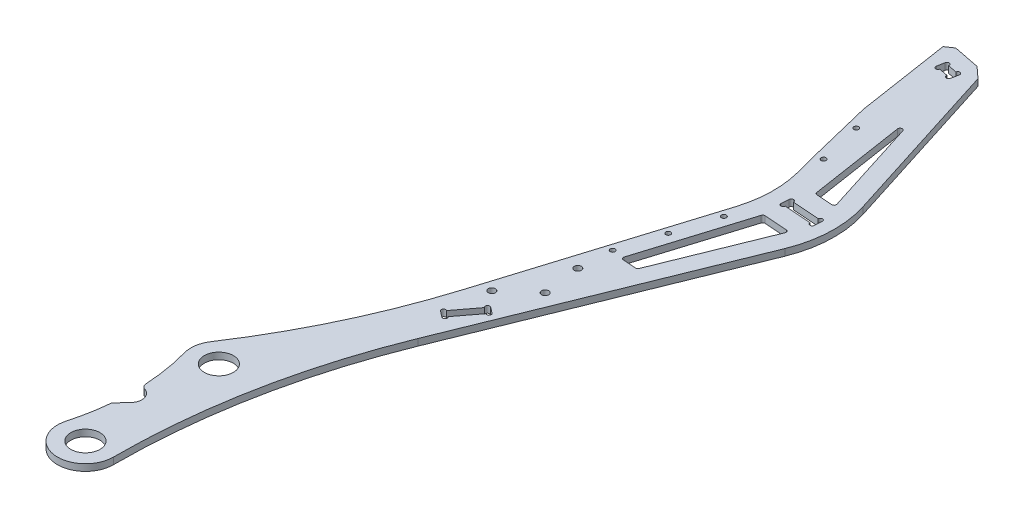
SolidWorks part; units mm, degrees
note: The reader was unsure of these and kept them because the rebuilt part matched: shared geometry of "草图7<3>".
material "碳板"
ref_plane "前视基准面" through (0, 0, 0) normal (0, 0, 1) x (1, 0, 0)
ref_plane "上视基准面" through (0, 0, 0) normal (0, 1, 0) x (1, 0, 0)
ref_plane "右视基准面" through (0, 0, 0) normal (1, 0, 0) x (0, 0, -1)
sketch "草图1" plane through (0, 0, 0) normal (0, 1, 0) x (1, 0, 0)
  line L0 (98.8372, 468.2646) -> (138.372, 211.288) construction
  line L1 (-58.327, 371.8311) -> (-50.4447, 320.5961) construction
  line L3 (-369.7364, 0) -> (416.5856, 0) construction
  line L4 (82.5, 489.7909) -> (82.5, -147.2883) construction
  line L5 (82.5, 0) -> (82.5, -60)
  line L6 (82.5, 0) -> (141.6477, 191.0538)
  line L7 (141.6477, 191.0538) -> (127.4573, 249.3516)
  line L8 (-53.7093, 374.6988) -> (-44.882, 317.3209)
  line L9 (93.8953, 467.5044) -> (133.4302, 210.5277)
  line L10 (0, 453.0589) -> (0, 190) construction
  line L11 (0, 190) -> (0, 570.1788) construction
  arc A0 (98.8372, 468.2646) -> (-58.327, 371.8311) centre (0, 453.0589) ccw construction
  arc A1 (-50.4447, 320.5961) -> (138.372, 211.288) centre (0, 190) ccw construction
  arc A2 (93.8953, 467.5044) -> (-53.7093, 374.6988) centre (0, 453.0589) ccw
  arc A3 (-44.882, 317.3209) -> (133.4302, 210.5277) centre (0, 190) ccw
  point P6 (0, 50)
  dimension "D1" = 100
  dimension "D2" = 140
  dimension "D3" = 260
  dimension "D4" = 170
  dimension "D5" = 82.5
  dimension "D6" = 190
  dimension "D7" = 60
  dimension "D8" = 200
  dimension "D9" = 60
  dimension "D10" = 5
sketch "草图3" plane through (0, 0, 0) normal (0, 1, 0) x (1, 0, 0)
  line L1 (128.8685, 240.1789) -> (141.6477, 191.0538)
  line L3 (82.5, 0) -> (82.6627, 0.5254)
  line L4 (82.5, 0) -> (82.5, -60) construction
  line L5 (82.5, 0) -> (82.5, -60) construction
  line L6 (93.8953, 467.5044) -> (133.4302, 210.5277) construction
  line L7 (82.5, 200489.7909) -> (82.5, -200147.2883) construction
  line L8 (98.2597, 7.4607) -> (171.5712, 188.9129)
  line L9 (-200369.7364, 0) -> (200416.5856, 0) construction
  line L10 (93.8953, 467.5044) -> (133.4302, 210.5277) construction
  line L11 (140.881, 285.6943) -> (171.5712, 188.9129)
  line L12 (141.6477, 191.0538) -> (171.5712, 188.9129) construction
  line L13 (108.4299, 83.7565) -> (141.6477, 191.0538)
  line L15 (128.8685, 240.1789) -> (121.2656, 289.5975)
  line L16 (121.2656, 289.5975) -> (140.881, 285.6943)
  circle A0 centre (82.5, 0) radius 6.55
  circle A1 centre (82.5, -60) radius 6.55
  circle A2 centre (82.5, 0) radius 12.55
  circle A3 centre (82.5, -60) radius 12.55
  circle A4 centre (82.5, 0) radius 0.55
  circle A5 centre (82.5, -60) radius 0.55
  arc A6 (70.404, -3.3452) -> (70.404, -56.6548) centre (-25.9781, -30) cw
  arc A7 (94.596, -3.3452) -> (94.596, -56.6548) centre (190.9781, -30) ccw
  circle A8 centre (190.9781, -30) radius 100 construction
  arc A9 (72.0339, 6.9256) -> (108.4299, 83.7565) centre (-178.1508, 172.478) ccw
  arc A11 (98.2597, 7.4607) -> (94.596, -3.3452) centre (190.9781, -30) ccw
  arc A12 (-44.882, 317.3209) -> (133.4302, 210.5277) centre (0, 190) ccw construction
  arc A13 (-44.882, 317.3209) -> (133.4302, 210.5277) centre (0, 190) ccw construction
  dimension "D1" = 13.1
  dimension "D2" = 13.1
  dimension "D5" = 100
  dimension "D6" = 68
  dimension "D7" = 70
  dimension "D8" = 300
  dimension "D9" = 20
  dimension "D10" = 30
  dimension "D11" = 50
  dimension "D12" = 30
  dimension "D3" = 6
  dimension "D4" = 6
extrude "凸台-拉伸1" add sketch "草图3" along normal blind 3
sketch "草图7" plane through (0, 3, 0) normal (0, 1, 0) x (1, 0, 0)
  line L0 (82.5, -60) -> (82.5, 0) construction
  line L1 (82.5, -60) -> (77.2906, -30.4558) construction
  line L2 (77.2906, -30.4558) -> (99.9898, -30.4558) construction
  line L3 (91.4098, -39.2813) -> (73.5902, -39.2813) construction
  line L4 (91.1427, -24.2646) -> (73.8573, -24.2646) construction
  line L5 (78.0025, -34.4935) -> (73.5902, -39.2813)
  circle A0 centre (77.2906, -30.4558) radius 4.1
  arc A1 (70.404, -56.6548) -> (70.404, -3.3452) centre (-25.9781, -30) ccw construction
  arc A2 (70.404, -56.6548) -> (70.404, -3.3452) centre (-25.9781, -30) ccw
  arc A3 (78.0025, -34.4935) -> (73.5902, -39.2813) centre (78.9346, -39.7794) ccw
  arc A4 (76.5786, -26.4181) -> (73.8573, -24.2646) centre (76.1754, -24.1314) cw
  circle A5 centre (87.2906, -30.4558) radius 6
  arc A6 (98.2597, 7.4607) -> (94.596, -56.6548) centre (190.9781, -30) ccw construction
  arc A7 (98.2597, 7.4607) -> (94.596, -56.6548) centre (190.9781, -30) ccw
  arc A8 (91.4098, -39.2813) -> (92.6033, -33.2441) centre (102.1915, -38.2762) cw
  arc A9 (91.9191, -26.6379) -> (91.1427, -24.2646) centre (94.5585, -24.4608) cw
  arc M45 (70.404, -3.3452) -> (70.404, -56.6548) centre (-25.9781, -30) cw
  dimension "D3" = 8.2
  dimension "D4" = 10
  dimension "D5" = 12
  dimension "D1" = 30
  dimension "D2" = 10
extrude "切除-拉伸3" cut sketch "草图7" against normal through all contours A0 A4 A2 A3 | A0 | A3 A0 M45 | L5 A3
extrude "凸台-拉伸2" add sketch "草图7<3>" against normal up to surface (3 mm away) contours A5 A7 | A7 A8 A5 | A5 A9 A7 up to face at (98.8839, 0, -57.3362)
sketch "草图7<3>" plane through (0, 3, 0) normal (0, 1, 0) x (1, 0, 0) same geometry as "草图7"
chamfer "倒角1" distance 4 angle 45 1 edges at (121.2656, 1.5, -289.5975)
chamfer "倒角2" distance 4 angle 30 1 edges at (140.881, 1.5, -285.6943)
chamfer "倒角3" distance 4 angle 5 1 edges at (128.8685, 1.5, -240.1789)
sketch "草图8" plane through (0, 3, 0) normal (0, 1, 0) x (1, 0, 0)
  line L0 (-44.5998, 0) -> (256.1265, 0) construction
  line L1 (0, 309.0851) -> (0, -66.3837) construction
  line L2 (125.1887, 288.8168) -> (137.0892, 286.4488) construction
  line L3 (128.2602, 244.1324) -> (134.8884, 217.0376) construction
  line L4 (109.4063, 282.7808) -> (159.2558, 272.8616) construction
  line L5 (128.5011, 280.7146) -> (136.4454, 279.1338)
  line L6 (128.5011, 280.7146) -> (127.8376, 277.38)
  line L7 (136.4454, 279.1338) -> (135.7819, 275.7992)
  line L8 (127.8376, 277.38) -> (135.7819, 275.7992)
  line L9 (128.5011, 280.7146) -> (135.7819, 275.7992) construction
  line L10 (136.4454, 279.1338) -> (127.8376, 277.38) construction
  line L11 (141.6477, 191.0538) -> (171.5712, 188.9129) construction
  line L12 (146.6565, 192.3998) -> (162.7155, 191.2509)
  line L13 (146.6565, 192.3998) -> (146.4139, 189.0084)
  line L14 (162.7155, 191.2509) -> (162.4728, 187.8595)
  line L15 (146.4139, 189.0084) -> (162.4728, 187.8595)
  line L16 (146.6565, 192.3998) -> (162.4728, 187.8595) construction
  line L17 (162.7155, 191.2509) -> (146.4139, 189.0084) construction
  line L18 (112.6472, 68.8514) -> (134.9155, 98.1868) construction
  line L19 (98.2597, 7.4607) -> (171.5712, 188.9129) construction
  line L20 (111.7345, 70.4606) -> (121.4689, 83.2844)
  line L21 (111.7345, 70.4606) -> (114.4426, 68.4049)
  line L22 (121.4689, 83.2844) -> (124.1771, 81.2287)
  line L23 (114.4426, 68.4049) -> (124.1771, 81.2287)
  line L24 (111.7345, 70.4606) -> (124.1771, 81.2287) construction
  line L25 (121.4689, 83.2844) -> (114.4426, 68.4049) construction
  line L26 (82.5, 0) -> (141.6477, 191.0538) construction
  circle A0 centre (131.3688, 283.5087) radius 1.6 construction
  circle A1 centre (131.3688, 273.5087) radius 1.6 construction
  circle A2 centre (129.4819, 280.5194) radius 1
  circle A3 centre (135.4646, 279.329) radius 1
  circle A4 centre (128.8184, 277.1848) radius 1
  circle A5 centre (134.8011, 275.9944) radius 1
  circle A6 centre (147.654, 192.3284) radius 1
  circle A7 centre (147.4113, 188.9371) radius 1
  circle A8 centre (161.718, 191.3222) radius 1
  circle A9 centre (161.4754, 187.9309) radius 1
  circle A10 centre (112.3391, 71.2571) radius 1
  circle A11 centre (115.0472, 69.2014) radius 1
  circle A12 centre (120.8643, 82.4879) radius 1
  circle A13 centre (123.5724, 80.4322) radius 1
  point P17 (132.1415, 278.2569)
  point P30 (154.5647, 190.1297)
  point P53 (117.9558, 75.8447)
  dimension "D1" = 3.2
  dimension "D7" = 2
  dimension "D12" = 2
  dimension "D16" = 2
  dimension "D2" = 10
  dimension "D3" = 4
  dimension "D4" = 10
  dimension "D5" = 3.4
  dimension "D6" = 8.1
  dimension "D8" = 9
  dimension "D9" = 5
  dimension "D10" = 3.4
  dimension "D11" = 16.1
  dimension "D13" = 9
  dimension "D14" = 3.4
  dimension "D15" = 16.1
  dimension "D17" = 20
  dimension "D18" = 20
extrude "切除-拉伸4" cut sketch "草图8" against normal through all contours A10 | A11 | L20 L22 L23 L21 | A12 | A13 | L12 L14 L15 L13 | A6 | A7 | A8 | A9 | A0 | A1 | L5 L7 L8 L6 | A2 | A4 | A3 | A5
sketch "草图9" plane through (0, 3, 0) normal (0, 1, 0) x (1, 0, 0)
  line L0 (141.6477, 191.0538) -> (127.4573, 249.3516) construction
  line L1 (128.2602, 244.1324) -> (167.1315, 253.6413) construction
  line L2 (128.2602, 244.1324) -> (134.8884, 217.0376) construction
  line L3 (133.9806, 235.2368) -> (138.7107, 215.8042) construction
  line L4 (125.9732, 118) -> (115.3681, 89.937) construction
  line L5 (85.3658, -0.8872) -> (144.5135, 190.1666)
  line L6 (85.3658, -0.8872) -> (144.5135, 190.1666) construction
  line L7 (120.6706, 103.9685) -> (128.1541, 101.1405) construction
  line L10 (-200369.7364, 0) -> (200416.5856, 0) construction
  circle A0 centre (133.9806, 235.2368) radius 1.1
  circle A1 centre (138.7107, 215.8042) radius 1.1
  circle A3 centre (138.5987, 171.0612) radius 1.1
  circle A4 centre (132.684, 151.9558) radius 1.1
  circle A5 centre (126.7692, 132.8504) radius 1.1
  circle A6 centre (125.9732, 118) radius 1.6
  circle A7 centre (115.3681, 89.937) radius 1.6
  circle A8 centre (128.1541, 101.1405) radius 1.6
  dimension "D2" = 2.2
  dimension "D3" = 3
  dimension "D4" = 20
  dimension "D7" = 3.2
  dimension "D5" = 20
  dimension "D6" = 20
  dimension "D8" = 1.8
  dimension "D9" = 8
  dimension "D10" = 30
  dimension "D11" = 118
  dimension "D12" = 3
  dimension "D13" = 20
  dimension "D14" = 10
  dimension "D15" = 3.5
extrude "切除-拉伸5" cut sketch "草图9" against normal through all
sketch "草图11" plane through (0, 3, 0) normal (0, 1, 0) x (1, 0, 0)
  line L0 (141.6477, 191.0538) -> (171.5712, 188.9129) construction
  line L1 (141.5944, 256.9789) -> (150.2894, 200.4611)
  line L2 (150.2894, 200.4611) -> (159.7308, 199.7856)
  line L5 (128.2602, 244.1324) -> (121.7401, 286.5129) construction
  line L8 (146.8043, 180.6593) -> (159.2485, 179.769)
  line L9 (159.2485, 179.769) -> (139.5646, 131.0495)
  line L10 (139.5646, 131.0495) -> (131.6217, 131.6177)
  line L11 (131.6217, 131.6177) -> (146.8043, 180.6593)
  line L12 (108.4299, 83.7565) -> (141.6477, 191.0538) construction
  line L13 (98.2597, 7.4607) -> (171.5712, 188.9129) construction
  line L14 (159.7308, 199.7856) -> (141.5944, 256.9789)
  line L15 (142.0901, 281.8815) -> (171.5712, 188.9129) construction
  dimension "D1" = 10
  dimension "D2" = 8
  dimension "D3" = 60
  dimension "D5" = 10
  dimension "D6" = 8
  dimension "D7" = 8
  dimension "D8" = 50
fillet "圆角1" radius 50 2 edges at (141.6477, 1.5, -191.0538) (171.5712, 1.5, -188.9129)
extrude "切除-拉伸6" cut sketch "草图11" against normal through all
fillet "圆角2" radius 1 8 edges at (150.2894, 1.5, -200.4611) (159.7308, 1.5, -199.7856) (159.2485, 1.5, -179.769) (139.5646, 1.5, -131.0495) (131.6217, 1.5, -131.6177) (146.8043, 1.5, -180.6593) (73.5902, 1.5, 39.2813) (78.0025, 1.5, 34.4935)
fillet "圆角3" radius 1 1 edges at (141.5944, 1.5, -256.9789)
sketch "草图12" plane through (0, 3, 0) normal (0, 1, 0) x (1, 0, 0)
  line L0 (77.7873, -34.727) -> (73.8186, -39.0335) construction
  line L1 (82.5, -60) -> (123.2875, -60) construction
  line L2 (98.2597, 7.4607) -> (164.8289, 172.2252) construction
  line L3 (98.2597, 7.4607) -> (117.3452, 54.6988)
  arc A0 (81.3311, -29.7598) -> (76.5786, -26.4181) centre (77.2906, -30.4558) ccw construction
  arc A1 (81.3311, -29.7598) -> (76.5786, -26.4181) centre (77.2906, -30.4558) ccw
  arc A2 (81.3311, -29.7598) -> (81.3311, -31.1517) centre (87.2906, -30.4558) ccw construction
  arc A3 (81.3311, -29.7598) -> (81.3311, -31.1517) centre (87.2906, -30.4558) ccw
  arc A4 (95.05, -60) -> (117.3452, 54.6988) centre (401.2348, -60) cw
  arc A5 (78.2811, -34.4343) -> (81.3311, -31.1517) centre (77.2906, -30.4558) ccw construction
  arc A6 (78.2811, -34.4343) -> (81.3311, -31.1517) centre (77.2906, -30.4558) ccw
  arc A7 (78.2811, -34.4343) -> (77.7873, -34.727) centre (78.5226, -35.4047) ccw construction
  arc A8 (78.2811, -34.4343) -> (77.7873, -34.727) centre (78.5226, -35.4047) ccw
  arc A9 (73.8573, -24.2646) -> (76.5786, -26.4181) centre (76.1754, -24.1314) ccw construction
  arc A10 (75.5034, -26.354) -> (76.5786, -26.4181) centre (76.1754, -24.1314) ccw
  arc A11 (75.5034, -26.354) -> (77.7873, -34.727) centre (74.0212, -31.2563) cw
  arc A12 (70.404, -56.6548) -> (94.596, -56.6548) centre (82.5, -60) ccw construction
  arc A13 (98.2597, 7.4607) -> (91.1427, -24.2646) centre (190.9781, -30) ccw construction
  arc A14 (98.2597, 7.4607) -> (91.1427, -24.2646) centre (190.9781, -30) ccw
  arc A15 (91.1427, -24.2646) -> (91.9191, -26.6379) centre (94.5585, -24.4608) ccw construction
  arc A16 (91.1427, -24.2646) -> (91.9191, -26.6379) centre (94.5585, -24.4608) ccw
  arc A17 (92.6033, -33.2441) -> (91.9191, -26.6379) centre (87.2906, -30.4558) ccw construction
  arc A18 (92.6033, -33.2441) -> (91.9191, -26.6379) centre (87.2906, -30.4558) ccw
  arc A19 (92.6033, -33.2441) -> (91.4098, -39.2813) centre (102.1915, -38.2762) ccw construction
  arc A20 (92.6033, -33.2441) -> (91.4098, -39.2813) centre (102.1915, -38.2762) ccw
  arc A21 (91.4098, -39.2813) -> (94.596, -56.6548) centre (190.9781, -30) ccw construction
  arc A22 (91.4098, -39.2813) -> (94.596, -56.6548) centre (190.9781, -30) ccw
  arc A23 (95.05, -60) -> (94.596, -56.6548) centre (82.5, -60) ccw
extrude "凸台-拉伸3" add sketch "草图12" against normal up to surface (3 mm away) up to face at (151.3077, 0, -215.344)
move or copy body "实体-移动/复制1" [suppressed] bodies to move or copy 117
